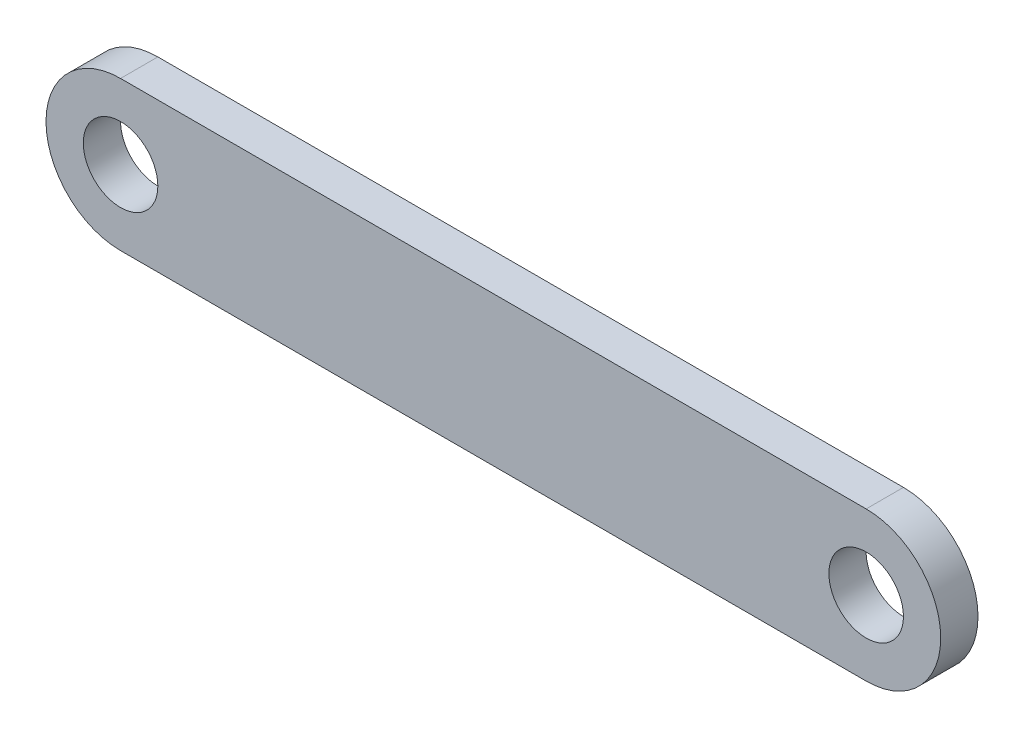
SolidWorks part; units mm, degrees
ref_plane "Front Plane" through (0, 0, 0) normal (0, 0, 1) x (1, 0, 0)
ref_plane "Top Plane" through (0, 0, 0) normal (0, 1, 0) x (1, 0, 0)
ref_plane "Right Plane" through (0, 0, 0) normal (1, 0, 0) x (0, 0, -1)
other "Configuration Table"
sketch "Sketch1" plane through (0, 0, 0) normal (0, 0, 1) x (1, 0, 0)
  line L0 (0, 0) -> (100, 0) construction
  line L1 (0, -10) -> (100, -10)
  line L2 (0, 10) -> (100, 10)
  line L3 (0, -10) -> (100, -10) construction
  arc A0 (0, 10) -> (0, -10) centre (0, 0) ccw
  arc A1 (100, 10) -> (100, -10) centre (100, 0) cw
  circle A2 centre (0, 0) radius 5
  circle A3 centre (100, 0) radius 5
  dimension "D4" = 10
  dimension "D3" = 100
  dimension "D1" = 10
  dimension "D2" = 10
extrude "Boss-Extrude1" add sketch "Sketch1" along normal blind 2.5 and the other way blind 2.5
ref_axis "Axis1" through (0, 0, -4.7408) along (0, 0, 1)
ref_axis "Axis2" through (100, 0, -5.7285) along (0, 0, 1)
equation "\"D4@Sketch1\"=\"D2@Sketch1\""
equation "\"D1@Sketch1\"=\"D2@Sketch1\""
